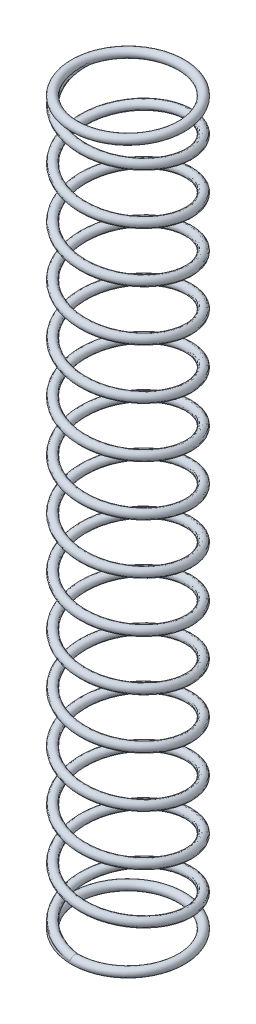
SolidWorks part; units mm, degrees
note: '?' marks a value the reader was unsure of.
other "Marquage1"
sketch "Esquisse72" plane through (-4.3104, 25.3, -4.5213) normal (0, 1, 0) x (1, 0, 0)
other "Marquage2"
sketch "Esquisse73" plane through (-4.3104, 25.3, -4.5213) normal (0, 1, 0) x (1, 0, 0)
ref_plane "Plan de face" through (0, 0, 0) normal (0, 0, 1) x (1, 0, 0)
ref_plane "Plan de dessus" through (0, 0, 0) normal (0, 1, 0) x (1, 0, 0)
ref_plane "Plan de droite" through (0, 0, 0) normal (1, 0, 0) x (0, 0, -1)
sketch "Esquisse1" plane through (0, 0, 0) normal (0, 1, 0) x (1, 0, 0)
  circle A0 centre (0, 0) radius 3.7
  dimension "D1" = 7.4
sketch "Esquisse16" plane through (0, 0, 0) normal (0, 1, 0) x (1, 0, 0)
  circle A2 centre (0, 0) radius 3.7
  circle A3 centre (0, 0) radius 3.7 construction
sweep "Balayage4" add path "Esquisse16" circular profile diameter 0.6 parameters "D3"=0.6
sketch "Esquisse59" plane through (0, 0, 0) normal (0, 1, 0) x (1, 0, 0)
  circle A0 centre (0, 0) radius 3.7
  circle A1 centre (0, 0) radius 3.7 construction
curve "Hélice/Spirale2" pitch 3.5 height 50 turns 14.2857
sweep "Balayage5" add path "Hélice/Spirale2" circular profile diameter 0.6 parameters "D3"=0.6
ref_plane "Plan1" through (0, 50, 0) normal (0, 1, 0) x (1, 0, 0)
sketch "Esquisse68" plane through (0, 50, 0) normal (0, 1, 0) x (1, 0, 0)
  circle A0 centre (0, 0) radius 3.7
  circle A1 centre (0, 0) radius 3.7 construction
sweep "Balayage8" add path "Esquisse68" circular profile diameter 0.6 parameters "D3"=0.6
ref_axis "Axe1" through (0, 26.58, 0) along (0, -1, 0)?
equation "\"D1@Esquisse1\"=\"outer_diameter\"-\"wire_diameter\""
equation "\"wire_diameter\"= 0.6"
equation "\"D3@Balayage4\"=\"wire_diameter\""
equation "\"D3@Balayage5\"=\"wire_diameter\""
equation "\"D3@Balayage8\"=\"wire_diameter\""
equation "\"outer_diameter\"=8"
